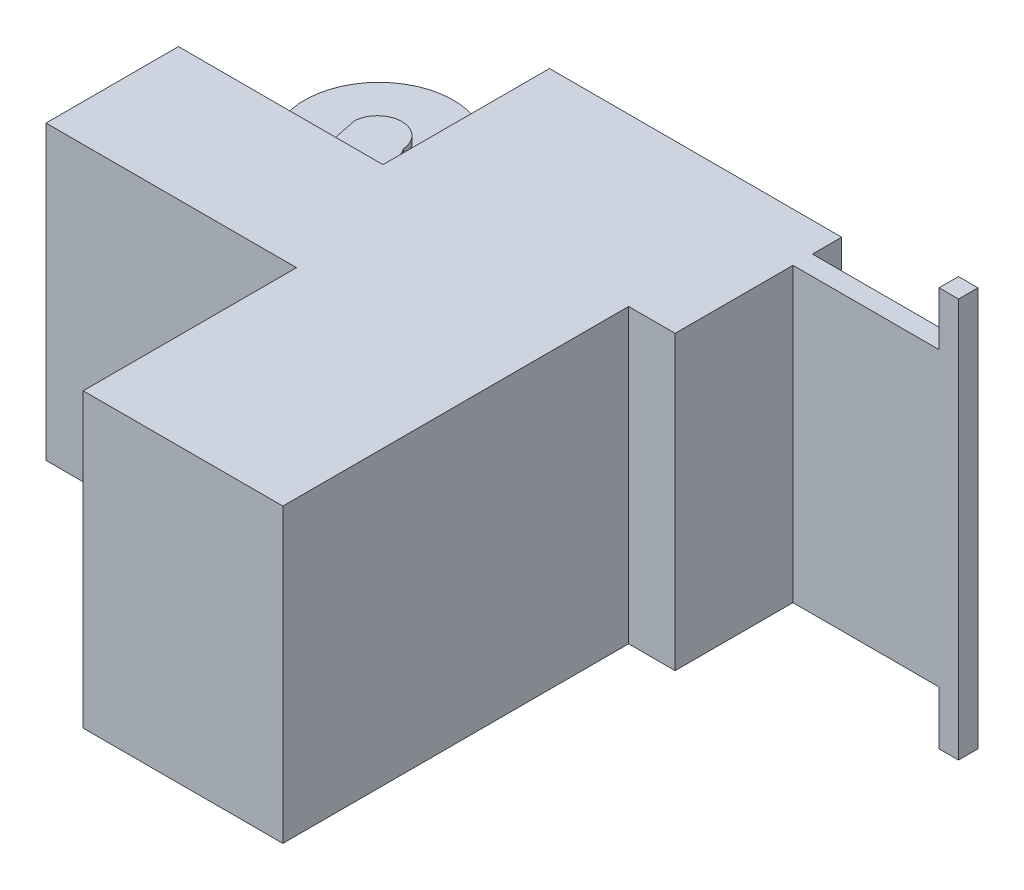
SolidWorks part; units mm, degrees
ref_plane "正面" through (0, 0, 0) normal (0, 0, 1) x (1, 0, 0)
ref_plane "平面" through (0, 0, 0) normal (0, 1, 0) x (1, 0, 0)
ref_plane "右側面" through (0, 0, 0) normal (1, 0, 0) x (0, 0, -1)
sketch "ｽｹｯﾁ1" plane through (0, 0, 0) normal (1, 0, 0) x (0, 0, -1)
  line L1 (-44.3523, 138.7889) -> (255.6477, 138.7889)
  line L2 (-44.3523, 138.7889) -> (-44.3523, -32.2111)
  line L3 (-44.3523, -32.2111) -> (255.6477, -32.2111)
  line L4 (255.6477, 138.7889) -> (255.6477, -32.2111)
extrude "ﾎﾞｽ - 押し出し1" add sketch "ｽｹｯﾁ1" along normal blind 300
sketch "ｽｹｯﾁ2" plane through (0, 138.7889, 0) normal (0, 1, 0) x (1, 0, 0)
  line L0 (300, 255.6477) -> (0, 255.6477) construction
  line L1 (300, -44.3523) -> (252.2101, -44.3523)
  line L2 (300, -44.3523) -> (300, 255.6477)
  line L3 (300, 255.6477) -> (252.2101, 255.6477)
  line L4 (252.2101, -44.3523) -> (252.2101, 255.6477)
  line L6 (0, -44.3523) -> (47.2101, -44.3523)
  line L7 (0, -44.3523) -> (0, 255.6477)
  line L8 (0, 255.6477) -> (47.2101, 255.6477)
  line L9 (47.2101, -44.3523) -> (47.2101, 255.6477)
  line L10 (252.2101, -44.3523) -> (47.2101, -44.3523)
  line L11 (252.2101, -44.3523) -> (252.2101, 255.6477)
  line L12 (252.2101, 255.6477) -> (47.2101, 255.6477)
  line L13 (47.2101, -44.3523) -> (47.2101, 255.6477)
  line M4 (0, -44.3523) -> (300, -44.3523)
  line M6 (300, 255.6477) -> (0, 255.6477)
extrude "ﾎﾞｽ - 押し出し2" add sketch "ｽｹｯﾁ2" along normal blind 355 contours L9 L4 M4 M6 region at (149.7101, 138.7889, -105.6477)
sketch "ｽｹｯﾁ3" plane through (47.2101, 0, 0) normal (-1, 0, 0) x (0, 0, 1)
  line L0 (-255.6477, 493.7889) -> (-255.6477, 138.7889) construction
  line L1 (44.3523, 138.7889) -> (-255.6477, 138.7889)
  line L2 (44.3523, 138.7889) -> (44.3523, 274.7889)
  line L3 (44.3523, 274.7889) -> (-255.6477, 274.7889)
  line L4 (-255.6477, 138.7889) -> (-255.6477, 274.7889)
extrude "ﾎﾞｽ - 押し出し3" add sketch "ｽｹｯﾁ3" along normal blind 257.2101
sketch "ｽｹｯﾁ4" plane through (0, 138.7889, 0) normal (0, -1, 0) x (1, 0, 0)
  line L2 (-141.9604, -105.6477) -> (-141.9604, -45.6477)
  line L3 (-141.9604, -45.6477) -> (-21.9604, -45.6477)
  line L4 (-21.9604, -45.6477) -> (-21.9604, -165.6477)
  line L5 (-21.9604, -165.6477) -> (-141.9604, -165.6477)
  line L6 (-141.9604, -165.6477) -> (-141.9604, -105.6477)
extrude "ﾎﾞｽ - 押し出し4" add sketch "ｽｹｯﾁ4" along normal blind 24
sketch "ｽｹｯﾁ5" plane through (0, 114.7889, 0) normal (0, -1, 0) x (1, 0, 0)
  line L0 (-141.9604, -105.6477) -> (-141.9604, -136.6477)
  line L1 (-141.9604, -45.6477) -> (-141.9604, -165.6477) construction
  line L2 (-141.9604, -105.6477) -> (-141.9604, -74.6477)
  line L3 (-141.9604, -136.6477) -> (-21.9604, -136.6477)
  line L4 (-21.9604, -165.6477) -> (-21.9604, -45.6477) construction
  line L5 (-21.9604, -136.6477) -> (-21.9604, -74.6477)
  line L6 (-21.9604, -74.6477) -> (-141.9604, -74.6477)
extrude "ﾎﾞｽ - 押し出し5" add sketch "ｽｹｯﾁ5" along normal blind 120
sketch "ｽｹｯﾁ6" plane through (0, 0, -136.6477) normal (0, 0, -1) x (-1, 0, 0)
  line L0 (81.9604, 114.7889) -> (147.6427, 114.7889)
  line L1 (141.9604, 114.7889) -> (21.9604, 114.7889) construction
  line L2 (147.6427, 114.7889) -> (147.6427, -4.3666)
  line L3 (147.6427, -4.3666) -> (172.6427, -4.3666)
  line L4 (147.6427, -4.3666) -> (122.6427, -4.3666)
  line L5 (122.6427, -4.3666) -> (81.9604, 114.7889)
  line L6 (172.6427, -4.3666) -> (147.6427, 114.7889)
  arc A0 (172.6427, -4.3666) -> (122.6427, -4.3666) centre (147.6427, -3.2401) cw
extrude "ﾎﾞｽ - 押し出し7" add sketch "ｽｹｯﾁ6" against normal blind 62 contours L3 L6 L2 | A0 L3 L4 L1 L2 | L4 L2 L0 L1 | L5 L4 L1 L3 region at (-123.4512, 64.1205, -136.6477) region at (-147.6427, -14.4725, -136.6477) region at (-155.976, 35.3519, -136.6477)
sketch "ｽｹｯﾁ8" plane through (0, 0, -136.6477) normal (0, 0, -1) x (-1, 0, 0)
  line L0 (122.6951, -5.2111) -> (55.5391, 114.7889)
  line L1 (141.9604, 114.7889) -> (21.9604, 114.7889) construction
  line L2 (55.5391, 114.7889) -> (21.9604, 114.7889)
  line L3 (21.9604, 114.7889) -> (21.9604, -5.2111)
  line L4 (21.9604, -5.2111) -> (21.9604, 114.7889) construction
  line L5 (122.6951, -5.2111) -> (21.9604, -5.2111) construction
  line L6 (21.9604, -5.2111) -> (122.6951, -5.2111)
extrude "ｶｯﾄ - 押し出し3" cut sketch "ｽｹｯﾁ8" against normal blind 133
sketch "ｽｹｯﾁ9" plane through (0, 0, -136.6477) normal (0, 0, -1) x (-1, 0, 0)
  line L0 (122.6951, -5.2111) -> (172.6427, -4.3666)
  circle A0 centre (147.6689, -4.7889) radius 76.5
  point P0 (147.6689, -4.7889)
  line M2 (55.5391, 114.7889) -> (122.6951, -5.2111)
  arc M3 (122.6951, -5.2111) -> (172.6427, -4.3666) centre (147.6427, -3.2401) ccw
  line M4 (172.6427, -4.3666) -> (147.6427, 114.7889)
extrude "ﾎﾞｽ - 押し出し9" add sketch "ｽｹｯﾁ9" against normal blind 62 separate body contours A0 M2 M4 M3 region at (-148.1023, -30.4215, -136.6477)
sketch "ｽｹｯﾁ11" plane through (0, 0, -136.6477) normal (0, 0, -1) x (-1, 0, 0)
  line L0 (156.7955, 71.1648) -> (172.6427, -4.3666)
  line L1 (92.6899, 48.4047) -> (122.6951, -5.2111)
  arc A0 (122.6951, -5.2111) -> (172.6427, -4.3666) centre (147.6427, -3.2401) ccw
  arc A1 (92.6899, 48.4047) -> (156.7955, 71.1648) centre (147.6689, -4.7889) ccw
extrude "ｶｯﾄ - 押し出し4" cut sketch "ｽｹｯﾁ11" against normal blind 7.5
sketch "ｽｹｯﾁ12" plane through (0, 0, -74.6477) normal (0, 0, 1) x (1, 0, 0)
  line L0 (-156.7955, 71.1648) -> (-172.6427, -4.3666)
  line L1 (-122.6951, -5.2111) -> (-92.6899, 48.4047)
  arc A0 (-172.6427, -4.3666) -> (-122.6951, -5.2111) centre (-147.6427, -3.2401) ccw
  arc A1 (-156.7955, 71.1648) -> (-92.6899, 48.4047) centre (-147.6689, -4.7889) ccw
extrude "ｶｯﾄ - 押し出し5" cut sketch "ｽｹｯﾁ12" against normal blind 7.5
sketch "ｽｹｯﾁ13" plane through (300, 0, 0) normal (1, 0, 0) x (0, 0, -1)
  line L0 (-44.3523, 138.7889) -> (-44.3523, -32.2111) construction
  line L1 (255.6477, -32.2111) -> (-44.3523, -32.2111)
  line L2 (255.6477, -32.2111) -> (255.6477, -2.2111)
  line L3 (255.6477, -2.2111) -> (-44.3523, -2.2111)
  line L4 (-44.3523, -32.2111) -> (-44.3523, -2.2111)
  line L5 (-44.3523, -2.2111) -> (-44.3523, 17.7889)
  line L6 (-44.3523, 17.7889) -> (255.6477, 17.7889)
  line L7 (255.6477, -32.2111) -> (255.6477, 138.7889) construction
  line L8 (255.6477, 17.7889) -> (255.6477, -2.2111)
  line M5 (-44.3523, 138.7889) -> (-44.3523, -32.2111)
  line M7 (255.6477, -32.2111) -> (255.6477, 138.7889)
extrude "ﾎﾞｽ - 押し出し10" add sketch "ｽｹｯﾁ13" along normal blind 170 contours L6 L3 M5 M7 region at (300, 7.7889, -105.6477)
sketch "ｽｹｯﾁ14" plane through (0, 0, 44.3523) normal (0, 0, 1) x (1, 0, 0)
  line L0 (470, -2.2111) -> (450, -2.2111)
  line L1 (470, -2.2111) -> (300, -2.2111) construction
  line L2 (450, -2.2111) -> (450, 17.7889)
  line L3 (470, 17.7889) -> (300, 17.7889) construction
  line L4 (450, 17.7889) -> (470, 17.7889)
  line L5 (470, 17.7889) -> (470, -2.2111)
extrude "ﾎﾞｽ - 押し出し11" add sketch "ｽｹｯﾁ14" along normal blind 55
sketch "ｽｹｯﾁ15" plane through (0, 0, -255.6477) normal (0, 0, -1) x (-1, 0, 0)
  line L0 (-470, 17.7889) -> (-450, 17.7889)
  line L1 (-470, 17.7889) -> (-300, 17.7889) construction
  line L2 (-450, 17.7889) -> (-450, -2.2111)
  line L3 (-470, -2.2111) -> (-300, -2.2111) construction
  line L4 (-450, -2.2111) -> (-470, -2.2111)
  line L5 (-470, -2.2111) -> (-470, 17.7889)
extrude "ﾎﾞｽ - 押し出し13" add sketch "ｽｹｯﾁ15" along normal blind 55
move or copy body "ﾎﾞﾃﾞｨ-移動/ｺﾋﾟｰ2" bodies to move or copy 118 114 copy no rotation origin (0, 112.8634, -105.6477) rotation axis (1, 0, 0) rotation angle 90
move or copy body "ﾎﾞﾃﾞｨ-移動/ｺﾋﾟｰ3" bodies to move or copy 120 121 copy no translate (-212, -150, 38)
